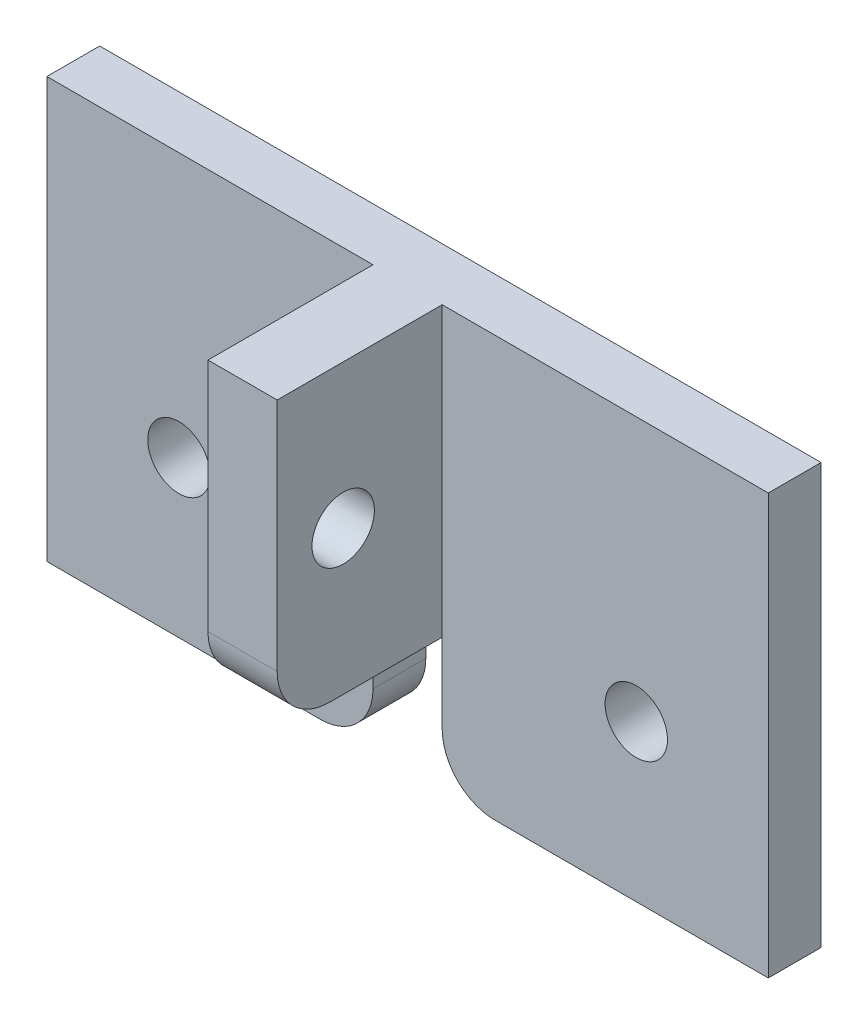
SolidWorks part; units mm, degrees
ref_plane "Front Plane" through (0, 0, 0) normal (0, 0, 1) x (1, 0, 0)
ref_plane "Top Plane" through (0, 0, 0) normal (0, 1, 0) x (1, 0, 0)
ref_plane "Right Plane" through (0, 0, 0) normal (1, 0, 0) x (0, 0, -1)
sketch "Sketch1" plane through (0, 0, 0) normal (0, 0, 1) x (1, 0, 0)
  line L0 (0, 10.102) -> (0, -10.102) construction
  line L1 (-17.35, 10.102) -> (17.35, 10.102)
  line L2 (-17.35, 10.102) -> (-17.35, -10.102)
  line L3 (-17.35, -10.102) -> (17.35, -10.102)
  line L4 (17.35, 10.102) -> (17.35, -10.102)
  line L5 (-17.35, -3.752) -> (17.35, -3.752) construction
  line L6 (-1.6637, -10.102) -> (-1.6637, -3.752)
  line L7 (-1.6637, -3.752) -> (1.6637, -3.752)
  line L8 (1.6637, -3.752) -> (1.6637, -10.102)
  line L9 (-11, -2.598) -> (11, -2.598) construction
  circle A0 centre (-11, -2.598) radius 1.5
  circle A1 centre (11, -2.598) radius 1.5
  point P6 (1.9004, -0.577)
  point P14 (0, -3.752)
  point P19 (0, -2.598)
  point P23 (0, 0)
  dimension "D3" = 3
  dimension "D1" = 22
  dimension "D2" = 1.154
  dimension "D4" = 12.7
  dimension "D5" = 6.35
  dimension "D6" = 3.3274
  dimension "D7" = 6.35
extrude "Boss-Extrude1" add sketch "Sketch1" along normal blind 2.54 contours L7 L8 L3 L4 L1 L2 L6 A1 A0 region at (0, 0.275, 0)
sketch "Sketch2" plane through (0, 0, 2.54) normal (0, 0, 1) x (1, 0, 0)
  line L0 (-17.35, 10.102) -> (17.35, 10.102) construction
  line L1 (-1.6637, -3.752) -> (1.6637, -3.752)
  line L2 (-1.6637, -3.752) -> (-1.6637, 10.102)
  line L3 (-1.6637, 10.102) -> (1.6637, 10.102)
  line L4 (1.6637, -3.752) -> (1.6637, 10.102)
  point P7 (1.6637, -0.577)
extrude "Boss-Extrude2" add sketch "Sketch2" along normal blind 7.9375
sketch "Sketch3" plane through (-1.6637, 0, 0) normal (-1, 0, 0) x (0, 0, 1)
  line L0 (10.4775, 10.102) -> (10.4775, -3.752) construction
  line L2 (2.54, 10.102) -> (2.54, -10.102) construction
  circle A1 centre (7.3025, 3.175) radius 1.5
  point P0 (5.5663, 2.9611)
  point P5 (10.4775, 3.175)
  dimension "D1" = 3
  dimension "D2" = 4.7625
extrude "Cut-Extrude1" cut sketch "Sketch3" against normal through all
fillet "Fillet1" radius 2.54 1 edges at (0, -3.752, 10.4775)
fillet "Fillet3" radius 2.54 2 edges at (1.6637, -10.102, 1.27) (-1.6637, -10.102, 1.27)
equation "\"bottomThickness\"= .220in"
equation "\"wallThickness\"= .125in"
equation "\"D6@Sketch1\"=\"wallThickness\"+.006in"
